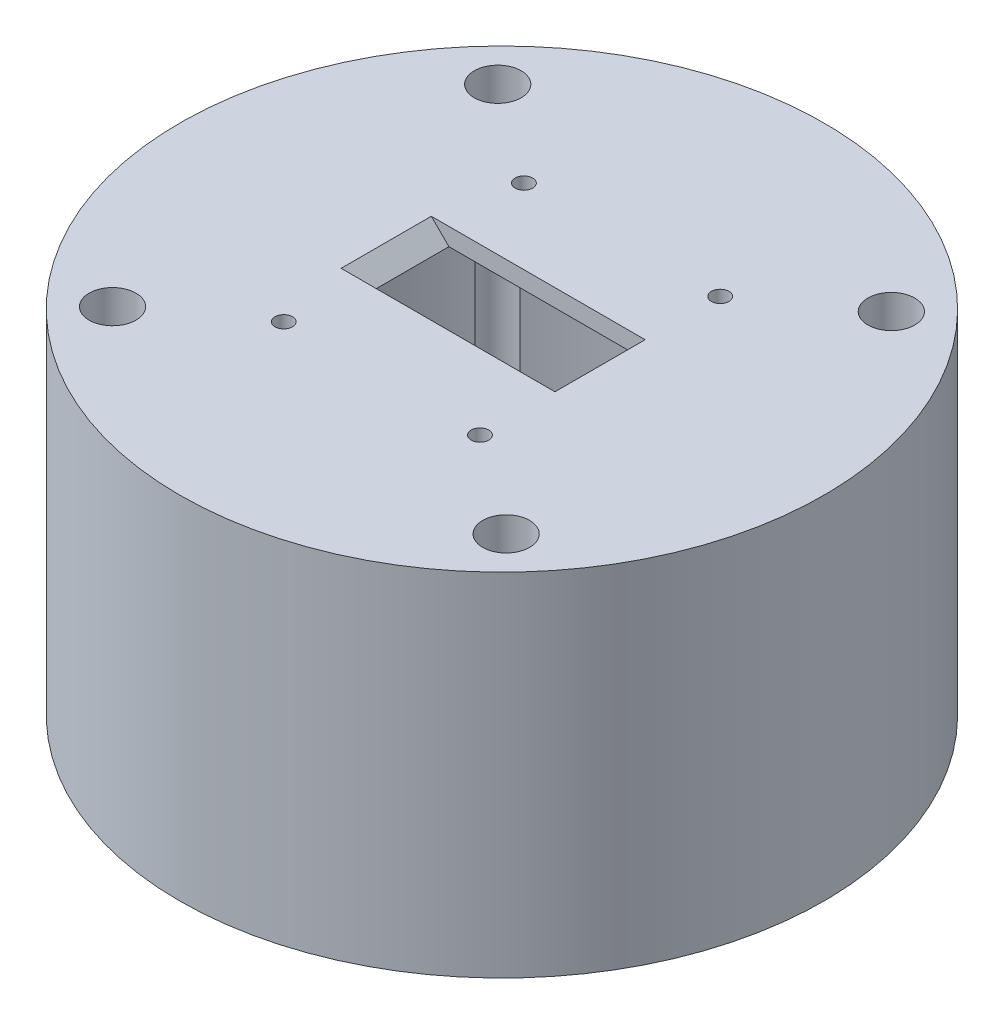
SolidWorks part; units mm, degrees
ref_plane "Спереди" through (0, 0, 0) normal (0, 0, 1) x (1, 0, 0)
ref_plane "Сверху" through (0, 0, 0) normal (0, 1, 0) x (1, 0, 0)
ref_plane "Справа" through (0, 0, 0) normal (1, 0, 0) x (0, 0, -1)
sketch "Эскиз1" plane through (0, 0, 0) normal (0, 1, 0) x (1, 0, 0)
  circle A0 centre (0, 0) radius 55
  dimension "D1" = 110
extrude "Бобышка-Вытянуть1" add sketch "Эскиз1" along normal blind 60
sketch "Эскиз2" plane through (0, 0, 0) normal (0, -1, 0) x (1, 0, 0)
  circle A0 centre (0, 0) radius 50
  dimension "D1" = 100
extrude "Вырез-Вытянуть1" cut sketch "Эскиз2" against normal blind 50
sketch "Эскиз3" plane through (0, 50, 0) normal (0, -1, 0) x (1, 0, 0)
  line L1 (-16.75, -7.7) -> (16.75, -7.7)
  line L2 (-16.75, -7.7) -> (-16.75, 7.7)
  line L3 (-16.75, 7.7) -> (16.75, 7.7)
  line L4 (16.75, -7.7) -> (16.75, 7.7)
  line L5 (-16.75, -7.7) -> (16.75, 7.7) construction
  line L6 (-16.75, 7.7) -> (16.75, -7.7) construction
  point P0 (0, 0)
  dimension "D1" = 15.4
  dimension "D2" = 33.5
extrude "Вырез-Вытянуть2" cut sketch "Эскиз3" against normal through all
sketch "Эскиз4" plane through (0, 60, 0) normal (0, 1, 0) x (1, 0, 0)
  line L0 (-16.75, 20.5) -> (-16.75, -20.5) construction
  line L1 (-16.75, -20.5) -> (16.75, -20.5) construction
  line L2 (16.75, -20.5) -> (16.75, 20.5) construction
  line L3 (16.75, 20.5) -> (-16.75, 20.5) construction
  line L4 (-23.35, 22.85) -> (23.35, 22.85) construction
  line L5 (16.75, -20.5) -> (-16.75, 20.5) construction
  line L6 (16.75, 20.5) -> (-16.75, -20.5) construction
  line L7 (23.35, 22.85) -> (23.35, -22.85) construction
  line L8 (39.3095, -38.4677) -> (-39.3095, 38.4677) construction
  line L9 (23.35, -22.85) -> (-23.35, -22.85) construction
  line L10 (-23.35, -22.85) -> (-23.35, 22.85) construction
  line L11 (16.75, 7.7) -> (16.75, -7.7) construction
  line L13 (23.35, -22.85) -> (-23.35, 22.85) construction
  line L14 (-16.75, -7.7) -> (-16.75, 7.7) construction
  line L15 (39.3095, 38.4677) -> (-39.3095, -38.4677) construction
  line L16 (23.35, 22.85) -> (-23.35, -22.85) construction
  circle A0 centre (-16.75, 20.5) radius 1.5
  circle A1 centre (16.75, 20.5) radius 1.5
  circle A2 centre (-16.75, -20.5) radius 1.5
  circle A3 centre (16.75, -20.5) radius 1.5
  circle A4 centre (0, 0) radius 55 construction
  circle A5 centre (33.5917, -32.8724) radius 4
  circle A6 centre (-33.5917, -32.8724) radius 4
  circle A7 centre (-33.5917, 32.8724) radius 4
  circle A8 centre (33.5917, 32.8724) radius 4
  point P0 (0, 0)
  point P5 (0, 0)
  point P27 (-16.75, 0)
  point P29 (16.75, 0)
  point P33 (-16.75, 0)
  dimension "D3" = 3
  dimension "D4" = 8
  dimension "D1" = 46.7
  dimension "D2" = 41
  dimension "D5" = 8
  dimension "D6" = 8
  dimension "D7" = 8
  dimension "D8" = 8
  dimension "D9" = 45.7
  dimension "D10" = 33.5
extrude "Вырез-Вытянуть3" cut sketch "Эскиз4" against normal through all
sketch "Эскиз6" plane through (0, 50, 0) normal (0, -1, 0) x (1, 0, 0)
  line L1 (-22.5, -32.5) -> (22.5, -32.5)
  line L2 (-32.5, -22.5) -> (-32.5, 22.5)
  line L3 (-22.5, 32.5) -> (22.5, 32.5)
  line L4 (32.5, -22.5) -> (32.5, 22.5)
  line L5 (-32.5, -32.5) -> (32.5, 32.5) construction
  line L6 (-32.5, 32.5) -> (32.5, -32.5) construction
  arc A0 (32.5, 22.5) -> (22.5, 32.5) centre (22.5, 22.5) ccw
  arc A1 (32.5, -22.5) -> (22.5, -32.5) centre (22.5, -22.5) cw
  arc A2 (-32.5, 22.5) -> (-22.5, 32.5) centre (-22.5, 22.5) cw
  arc A3 (-32.5, -22.5) -> (-22.5, -32.5) centre (-22.5, -22.5) ccw
  point P0 (0, 0)
  dimension "D3" = 10
  dimension "D1" = 65
  dimension "D2" = 65
extrude "Вырез-Вытянуть4" cut sketch "Эскиз6" against normal blind 7
chamfer "Фаска1" distance 3 angle 45 1 edges at (-16.75, 60, 0)
